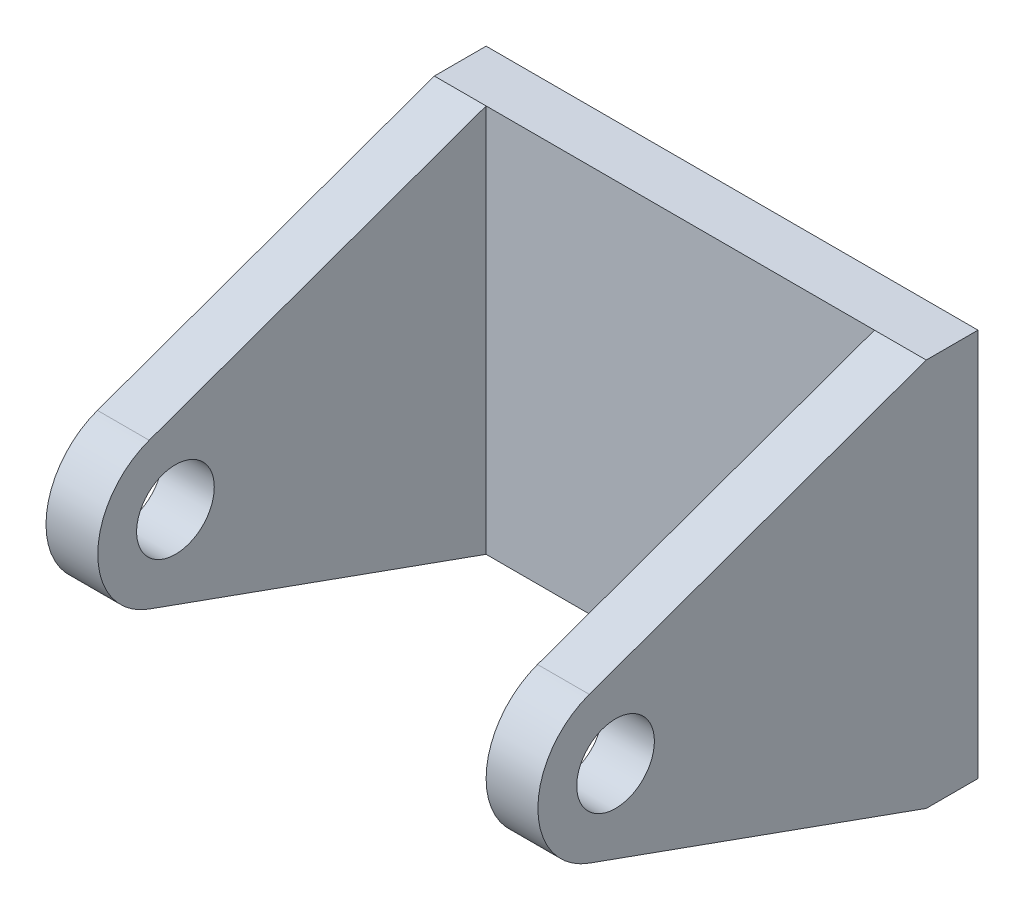
SolidWorks part; units mm, degrees
ref_plane "Front Plane" through (0, 0, 0) normal (1, 0, 0) x (0, 1, 0)
ref_plane "Top Plane" through (0, 0, 0) normal (0, 0, 1) x (0, 1, 0)
ref_plane "Right Plane" through (0, 0, 0) normal (0, 1, 0) x (-1, 0, 0)
sketch "Sketch1" plane through (0, 0, 0) normal (1, 0, 0) x (0, 1, 0)
  line L0 (-37.5, -60) -> (37.5, -60)
  line L1 (0, 0) -> (0, -60) construction
  line L2 (-37.5, -60) -> (-14.1162, 5.0726)
  line L3 (37.5, -60) -> (14.1162, 5.0726)
  circle A0 centre (0, 0) radius 7.5
  circle A1 centre (0, 0) radius 15
  point P9 (0, 0)
  point P10 (0, 0)
  dimension "D1" = 15
  dimension "D2" = 30
  dimension "D3" = 60
  dimension "D4" = 75
extrude "Boss-Extrude1" add sketch "Sketch1" along normal blind 10 contours L1 A1 L2 L0 | A0 A1 | A1 L1 L0 L3 region at (0, -15.0411, -37.4185) region at (0, 15.0411, -37.4185) region at (0, 0, 14.5757)
sketch "Sketch2" plane through (0, 0, -60) normal (0, 0, -1) x (1, 0, 0)
  line L0 (10, -37.5) -> (0, -37.5) construction
  line L1 (0, 37.5) -> (95, 37.5)
  line L2 (0, 37.5) -> (0, -37.5)
  line L3 (0, -37.5) -> (95, -37.5)
  line L4 (95, 37.5) -> (95, -37.5)
  dimension "D1" = 95
extrude "Boss-Extrude2" add sketch "Sketch2" along normal blind 10
pattern_linear "LPattern1" count 2 spacing 85 along (1, 0, 0) of "Boss-Extrude1"
